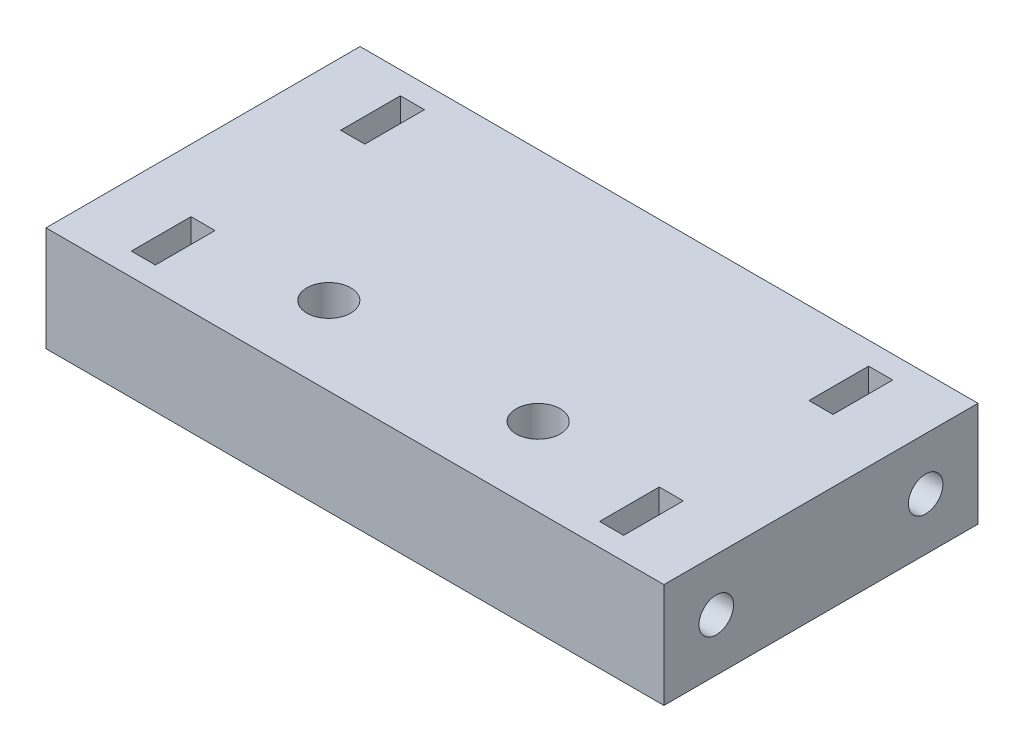
SolidWorks part; units mm, degrees
ref_plane "Front Plane" through (0, 0, 0) normal (0, 0, 1) x (1, 0, 0)
ref_plane "Top Plane" through (0, 0, 0) normal (0, 1, 0) x (1, 0, 0)
ref_plane "Right Plane" through (0, 0, 0) normal (1, 0, 0) x (0, 0, -1)
sketch "Sketch1" plane through (0, 0, 0) normal (0, 1, 0) x (1, 0, 0)
  line L1 (-29.5136, -15) -> (29.5136, -15)
  line L2 (-29.5136, -15) -> (-29.5136, 15)
  line L3 (-29.5136, 15) -> (29.5136, 15)
  line L4 (29.5136, -15) -> (29.5136, 15)
  line L5 (-29.5136, -15) -> (29.5136, 15) construction
  line L6 (-29.5136, 15) -> (29.5136, -15) construction
  point P0 (0, 0)
  dimension "D1" = 59.0272
  dimension "D2" = 30
extrude "Boss-Extrude1" add sketch "Sketch1" along normal blind 10
sketch "Sketch2" plane through (0, 10, 0) normal (0, 1, 0) x (1, 0, 0)
  line L0 (-10, -7.5) -> (10, -7.5) construction
  line L3 (0, 15) -> (0, -15) construction
  line L4 (29.5136, 15) -> (-29.5136, 15) construction
  line L5 (-29.5136, -15) -> (29.5136, -15) construction
  circle A0 centre (-10, -7.5) radius 2.1
  circle A1 centre (10, -7.5) radius 2.1
  point P3 (0, -7.5)
  dimension "D1" = 4.2
  dimension "D2" = 20
  dimension "D3" = 7.5
extrude "Cut-Extrude1" cut sketch "Sketch2" against normal through all
sketch "Sketch3" plane through (29.5136, 0, 0) normal (1, 0, 0) x (0, 0, -1)
  line L0 (0, 10) -> (0, 0) construction
  line L1 (-15, 10) -> (15, 10) construction
  line L2 (-15, 0) -> (15, 0) construction
  line L3 (-10, 5) -> (10, 5) construction
  circle A0 centre (-10, 5) radius 1.65
  circle A1 centre (10, 5) radius 1.65
  point P9 (0, 5)
  dimension "D2" = 3.3
  dimension "D1" = 20
extrude "Cut-Extrude2" cut sketch "Sketch3" against normal blind 12
sketch "Sketch4" plane through (-29.5136, 0, 0) normal (-1, 0, 0) x (0, 0, 1)
  line L0 (0, 10) -> (0, 0) construction
  line L3 (-10, 5) -> (10, 5) construction
  line L4 (-15, 10) -> (15, 10) construction
  circle A0 centre (-10, 5) radius 1.65
  circle A1 centre (10, 5) radius 1.65
  point P2 (0, 0)
  point P3 (0, 0)
  point P9 (0, 5)
  dimension "D2" = 3.3
  dimension "D1" = 20
extrude "Cut-Extrude3" cut sketch "Sketch4" against normal blind 12
ref_plane "Plane1" through (23.5136, 0, 0) normal (1, 0, 0) x (0, 0, -1)
ref_plane "Plane2" through (-23.5136, 0, 0) normal (-1, 0, 0) x (0, 0, 1)
sketch "Sketch5" plane through (23.5136, 0, 0) normal (1, 0, 0) x (0, 0, -1)
  line L0 (-12.85, 6.6454) -> (-12.85, 10)
  line L1 (-7.15, 6.6454) -> (-10, 8.2909) construction
  line L2 (-10, 8.2909) -> (-12.85, 6.6454) construction
  line L3 (-12.85, 6.6454) -> (-12.85, 3.3546)
  line L4 (-12.85, 3.3546) -> (-10, 1.7091)
  line L5 (-10, 1.7091) -> (-7.15, 3.3546)
  line L6 (-7.15, 3.3546) -> (-7.15, 6.6454)
  line L7 (10, 8.2909) -> (7.15, 6.6454) construction
  line L8 (7.15, 6.6454) -> (7.15, 3.3546)
  line L9 (7.15, 3.3546) -> (10, 1.7091)
  line L10 (10, 1.7091) -> (12.85, 3.3546)
  line L11 (12.85, 3.3546) -> (12.85, 6.6454)
  line L12 (12.85, 6.6454) -> (10, 8.2909) construction
  line L13 (-15, 10) -> (15, 10) construction
  line L14 (-12.85, 10) -> (-7.15, 10)
  line L15 (-7.15, 10) -> (-7.15, 6.6454)
  line L16 (7.15, 6.6454) -> (7.15, 10)
  line L17 (7.15, 10) -> (12.85, 10)
  line L18 (12.85, 10) -> (12.85, 6.6454)
  circle A0 centre (-10, 5) radius 2.85 construction
  circle A1 centre (10, 5) radius 2.85 construction
  dimension "D1" = 5.7
extrude "Cut-Extrude4" cut sketch "Sketch5" against normal blind 2.3
sketch "Sketch6" plane through (-23.5136, 0, 0) normal (-1, 0, 0) x (0, 0, 1)
  line L0 (-12.85, 6.6454) -> (-12.85, 10)
  line L1 (-7.15, 6.6454) -> (-10, 8.2909) construction
  line L2 (-10, 8.2909) -> (-12.85, 6.6454) construction
  line L3 (-12.85, 6.6454) -> (-12.85, 3.3546)
  line L4 (-12.85, 3.3546) -> (-10, 1.7091)
  line L5 (-10, 1.7091) -> (-7.15, 3.3546)
  line L6 (-7.15, 3.3546) -> (-7.15, 6.6454)
  line L7 (10, 8.2909) -> (7.15, 6.6454) construction
  line L8 (7.15, 6.6454) -> (7.15, 3.3546)
  line L9 (7.15, 3.3546) -> (10, 1.7091)
  line L10 (10, 1.7091) -> (12.85, 3.3546)
  line L11 (12.85, 3.3546) -> (12.85, 6.6454)
  line L12 (12.85, 6.6454) -> (10, 8.2909) construction
  line L14 (-12.85, 10) -> (-7.15, 10)
  line L15 (-7.15, 10) -> (-7.15, 6.6454)
  line L16 (7.15, 6.6454) -> (7.15, 10)
  line L17 (7.15, 10) -> (12.85, 10)
  line L18 (12.85, 10) -> (12.85, 6.6454)
  line L19 (-15, 10) -> (15, 10) construction
  circle A0 centre (-10, 5) radius 2.85 construction
  circle A1 centre (10, 5) radius 2.85 construction
  circle A2 centre (-10, 5) radius 1.65 construction
  circle A3 centre (-10, 5) radius 1.65 construction
  circle A5 centre (10, 5) radius 1.65 construction
  circle A6 centre (10, 5) radius 1.65 construction
  point P0 (15.2698, 5)
  point P10 (0, 0)
  point P28 (15.3553, 6.3088)
  point P30 (0, 0)
  dimension "D1" = 5.7
extrude "Cut-Extrude5" cut sketch "Sketch6" against normal blind 2.3
